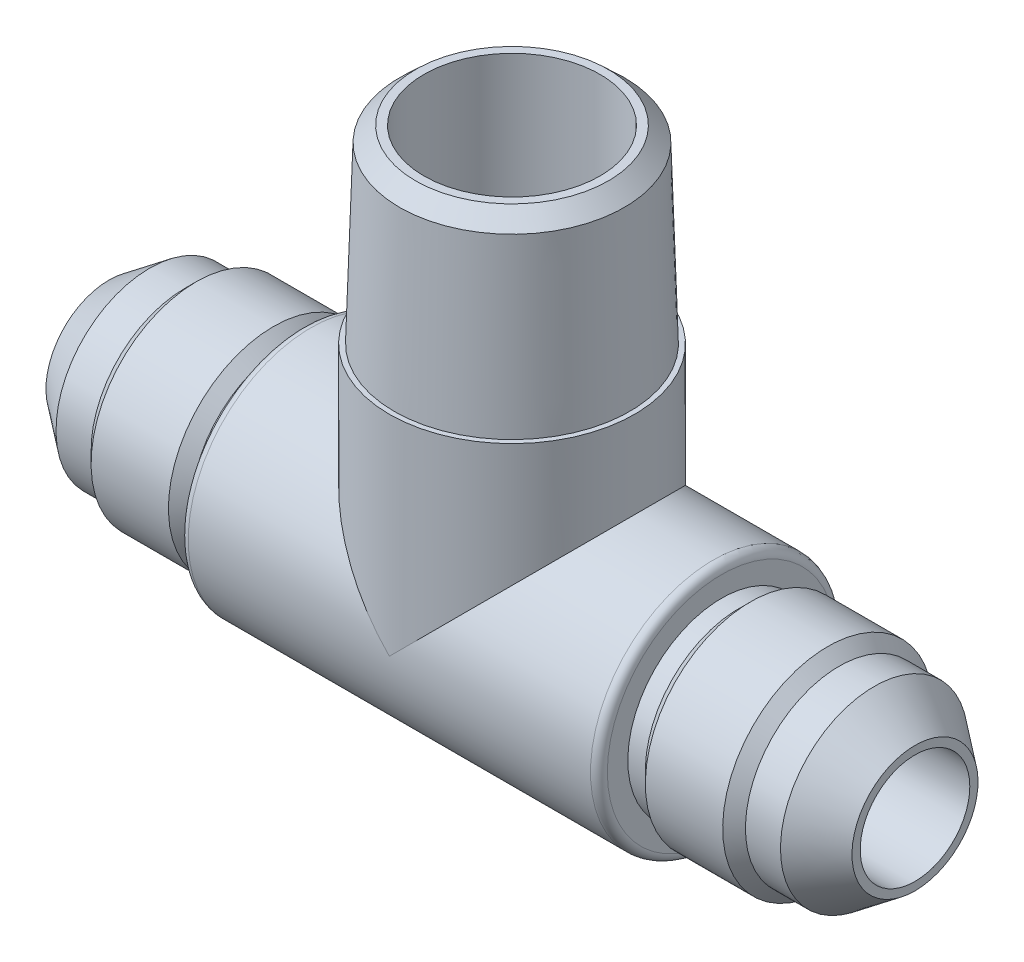
SolidWorks part; units mm, degrees
ref_plane "Front Plane" through (0, 0, 0) normal (0, 0, 1) x (1, 0, 0)
ref_plane "Top Plane" through (0, 0, 0) normal (0, 1, 0) x (1, 0, 0)
ref_plane "Right Plane" through (0, 0, 0) normal (1, 0, 0) x (0, 0, -1)
sketch "Sketch1" plane through (0, 0, 0) normal (0, 0, 1) x (1, 0, 0)
  line L0 (0, 0) -> (-18.9865, 0) construction
  line L1 (0, 0) -> (0, 18.9865) construction
  line L2 (-9.525, 18.9865) -> (9.525, 18.9865) construction
  line L3 (-18.9865, 9.525) -> (-18.9865, -9.525) construction
  line L6 (-36.5125, 9.525) -> (-36.5125, -9.525) construction
  line L8 (-10.668, 36.1163) -> (10.668, 36.1163) construction
  line L9 (0, 0) -> (0, 36.1163) construction
  line L10 (-18.9865, 11.1125) -> (-18.9865, -11.1125) construction
  line L12 (-11.1125, 18.9865) -> (11.1125, 18.9865) construction
  point P15 (0, 22.5603)
  dimension "S" = 17.526
  dimension "Pipe Thread Dia" = 21.336
  dimension "V" = 36.1163
  dimension "TE" = 13.556
  dimension "OA" = 22.225
ref_plane "Plane1" through (-36.5125, 0, 0) normal (1, 0, 0) x (0, 0, -1)
sketch "Sketch2" plane through (-36.5125, 0, 0) normal (1, 0, 0) x (0, 0, -1)
  circle A0 centre (0, 0) radius 9.525
  dimension "Thread OD" = 19.05
extrude "Extrude1" add sketch "Sketch2" along normal up to vertex (17.526 mm away) up to point (-18.9865, 0, 0)
sketch "Sketch3" plane through (-36.5125, 0, 0) normal (-1, 0, 0) x (0, 0, 1)
  circle A0 centre (0, 0) radius 9.525 construction
  circle A1 centre (0, 0) radius 9.525
curve "Helix/Spiral1" pitch 1.5875 height 36.5125 turns 23 parameters "pitch"=1.5875
sketch "Sketch4" plane through (0, 0, 0) normal (0, 0, 1) x (1, 0, 0)
  line L0 (-37.9016, 9.525) -> (-37.3062, 8.4939)
  line L1 (-37.3062, 8.4939) -> (-37.1078, 8.4939)
  line L2 (-37.1078, 8.4939) -> (-36.5125, 9.525)
  line L3 (-37.9016, 9.525) -> (-36.5125, 9.525)
  line L6 (-37.207, 9.525) -> (-37.207, 8.4939) construction
  line L7 (-37.6039, 9.0094) -> (-36.8102, 9.0094) construction
  line L8 (-36.5125, 9.525) -> (-36.5125, -9.525) construction
  dimension "D1" = 0.1984
  dimension "D2" = 0.7937
  dimension "D3" = 60
sweep "Cut-Sweep1" [suppressed] cut profiles "Sketch4" path "Helix/Spiral1"
sketch "Sketch5" plane through (0, 0, 0) normal (0, 0, 1) x (1, 0, 0)
  line L0 (-36.5125, 6.35) -> (-36.5125, -6.35) construction
  line L1 (-32.8189, 8.4939) -> (-29.6439, 8.4939)
  line L2 (-29.6439, 8.4939) -> (-28.6128, 9.525)
  line L3 (-36.5125, 5.7106) -> (-36.5125, -5.7106) construction
  line L4 (-28.6128, 9.525) -> (-36.5125, 9.525)
  line L5 (-37.9016, 9.525) -> (-36.5125, 9.525) construction
  line L6 (-18.9865, 9.525) -> (-18.9865, -9.525) construction
  line L7 (-18.9865, 8.4939) -> (-20.574, 8.4939)
  line L8 (-20.574, 8.4939) -> (-21.6051, 9.525)
  line L9 (-21.6051, 9.525) -> (-18.9865, 9.525)
  line L10 (-18.9865, 8.4939) -> (-18.9865, 9.525)
  line L11 (-27.2626, -9.525) -> (-27.2626, 0) construction
  line L12 (-18.9865, 0) -> (-36.5125, 0) construction
  line L13 (-36.5125, 9.525) -> (-36.5125, -9.525) construction
  line L14 (-36.5125, 5.7106) -> (-32.8189, 8.4939)
  line L15 (-36.5125, 9.525) -> (-36.5125, 5.7106)
  line L16 (0, 0) -> (-18.9865, 0) construction
  point P16 (-27.2626, -9.525)
  dimension "D3" = 45
  dimension "D5" = 45
  dimension "D6" = 1.5875
  dimension "Tube OD" = 12.7
  dimension "D2" = 11.4211
  dimension "D1" = 37
  dimension "D4" = 3.175
  dimension "D7" = 2.3813
revolve "Cut-Revolve1" cut sketch "Sketch5" angle 360 about L0
ref_plane "Plane2" through (-18.9865, 0, 0) normal (1, 0, 0) x (0, 0, -1)
sketch "Sketch15" plane through (-18.9865, 0, 0) normal (1, 0, 0) x (0, 0, -1)
  circle A0 centre (0, 0) radius 11.1125
extrude "Boss-Extrude1" add sketch "Sketch15" along normal up to vertex (18.9865 mm away) up to point (0, 0, 0)
sketch "Sketch16" plane through (0, 0, 0) normal (1, 0, 0) x (0, 0, -1)
  circle A0 centre (0, 0) radius 4.9657
  dimension "Min ID" = 9.9314
extrude "Cut-Extrude1" cut sketch "Sketch16" against normal through all
ref_plane "Plane3" through (0, 18.9865, 0) normal (0, 1, 0) x (-1, 0, 0)
sketch "Sketch20" plane through (0, 18.9865, 0) normal (0, 1, 0) x (-1, 0, 0)
  circle A0 centre (0, 0) radius 11.1125
extrude "Boss-Extrude2" add sketch "Sketch20" against normal up to vertex (18.9865 mm away) separate body up to point (0, 0, 0)
sketch "Sketch22" plane through (0, 18.9865, 0) normal (0, 1, 0) x (-1, 0, 0)
  circle A0 centre (0, 0) radius 10.668
extrude "Boss-Extrude3" add sketch "Sketch22" along normal up to vertex (17.1298 mm away) draft 1.75 separate body up to point (0, 36.1163, 0)
sketch "Sketch23" plane through (0, 36.1163, 0) normal (0, 1, 0) x (1, 0, 0)
  circle A0 centre (0, 0) radius 10.1446 construction
  circle A1 centre (0, 0) radius 10.1446
curve "Helix/Spiral2" parameters "Pitch"=1.8143
chamfer "Chamfer1" distance 1.3607 angle 45 1 edges at (0, 36.1163, 10.1446) first distance on face at (0, 36.1163, 10.1446)
sketch "Sketch25" plane through (0, 18.9865, 0) normal (0, -1, 0) x (1, 0, 0)
  circle A1 centre (0, 0) radius 10.668
  circle A2 centre (0, 0) radius 10.668
  dimension "D1" = 0
sketch "Sketch24" plane through (0, 0, 0) normal (0, 0, 1) x (1, 0, 0)
  line L0 (10.2428, 37.8738) -> (10.2428, 36.0596) construction
  line L1 (10.2428, 36.0596) -> (8.6716, 36.9667) construction
  line L2 (8.6716, 36.9667) -> (10.2428, 37.8738) construction
  line L3 (8.868, 37.0801) -> (8.868, 36.8533)
  line L4 (8.6716, 36.9667) -> (8.868, 36.9667) construction
  line L5 (10.0464, 37.7605) -> (10.0464, 36.173) construction
  line L6 (10.0464, 36.9667) -> (10.2428, 36.9667) construction
  line L7 (10.1446, 36.9667) -> (10.1446, 36.1163) construction
  line L8 (10.1446, 37.8172) -> (10.2428, 36.0596)
  line L9 (10.2428, 36.0596) -> (8.868, 36.8533)
  line L10 (8.868, 37.0801) -> (10.1446, 37.8172)
  dimension "D1" = 1.8143
  dimension "D2" = 0.2268
sweep "Cut-Sweep2" [suppressed] cut profiles "Sketch24" path "Helix/Spiral2"
extrude "Boss-Extrude4" add sketch "Sketch25" against normal up to vertex (17.1298 mm away) draft 15 up to point (10.668, 36.1163, 0)
sketch "Sketch28" plane through (0, 36.1163, 0) normal (0, 1, 0) x (1, 0, 0)
  circle A2 centre (0, 0) radius 7.9784
  circle A3 centre (0, 0) radius 7.9784
  dimension "D1" = 0.762
extrude "Cut-Extrude6" cut sketch "Sketch28" against normal up to vertex (17.1298 mm away) up to point (0, 18.9865, 0)
fillet "Fillet1" radius 0.762 1 edges at (-18.9865, 0, -11.1125)
sketch "Sketch10" plane through (0, 0, 0) normal (1, 0, 0) x (0, 0, -1)
  line L0 (0, 0) -> (-12.651, 0) construction
ref_axis "Axis1" through (0, 0, 12.651) along (0, 0, -1)
pattern_circular "CirPattern1" count 2 over 180 about axis through (0, 0, 12.651) along (0, 0, -1) reverse direction yes of bodies 110 103
combine bodies "Combine2" operation type add bodies to combine 110 122 114 105
sketch "Sketch30" plane through (0, 0, 0) normal (0, 0, 1) x (1, 0, 0)
  line L0 (0, 18.9865) -> (0, 9.4932)
  line L1 (0, 18.9865) -> (-10.922, 18.9865)
  line L2 (0, 0) -> (0, 18.9865) construction
  line L3 (-10.922, 18.9865) -> (0, 9.4932) construction
  line L4 (-5.461, 14.2399) -> (-6.1275, 13.4731) construction
  line L5 (-10.922, 18.9865) -> (-10.922, 18.4785)
  arc A0 (-10.922, 18.4785) -> (0, 9.4932) centre (13.649, 37.215) ccw
  point P2 (0, 9.4932)
  dimension "D1" = 0.254
  dimension "D2" = 1.016
  dimension "D3" = 0.508
revolve "Revolve1" add sketch "Sketch30" angle 360 about L0
sketch "Sketch26" plane through (-36.5125, 0, 0) normal (-1, 0, 0) x (0, 0, 1)
  circle A0 centre (0, 0) radius 4.9657 construction
  circle A1 centre (0, 0) radius 4.9657
extrude "Cut-Extrude4" cut sketch "Sketch26" against normal through all
sketch "Sketch29" plane through (0, 0, 0) normal (0, 1, 0) x (1, 0, 0)
  circle A0 centre (0, 0) radius 4.9657
  dimension "D1" = 9.9314
extrude "Cut-Extrude7" cut sketch "Sketch29" along normal through all
sketch "Sketch12" plane through (0, 0, 0) normal (0, 0, 1) x (1, 0, 0)
  line L0 (0, 0) -> (0, 36.1163) construction
  line L2 (0, 0) -> (-36.5125, 0) construction
  line L3 (7.9784, 36.1163) -> (-7.9784, 36.1163) construction
sketch "Sketch13" plane through (0, 0, 0) normal (1, 0, 0) x (0, 0, -1)
  line L0 (9.525, 18.9865) -> (-9.525, 18.9865)
  line L1 (0, 0) -> (0, 18.9865) construction
  line L3 (9.525, 0) -> (-9.525, 0)
  circle A0 centre (0, 0) radius 4.9657
  circle A1 centre (0, 0) radius 4.9657 construction
  dimension "D1" = 19.05
sketch "Sketch31" plane through (-36.5125, 0, 0) normal (-1, 0, 0) x (0, 0, 1)
  point P0 (0, 0)
sketch "Sketch32" plane through (36.5125, 0, 0) normal (1, 0, 0) x (0, 0, -1)
  point P0 (0, 0)
equation "\"D1@Sketch1\" = \"Thread OD@Sketch2\""
equation "\"D3@Helix/Spiral1\" = \"Q@Sketch1\""
equation "\"D1@Sketch4\" = \"pitch@Helix/Spiral1\"*.125"
equation "\"D2@Sketch4\" = \"pitch@Helix/Spiral1\"*.5"
equation "\"D6@Sketch5\" = \"pitch@Helix/Spiral1\"*1"
equation "\"D4@Sketch5\" = \"pitch@Helix/Spiral1\"*2"
equation "\"D1@Sketch13\" = \"D1@Sketch1\""
equation "\"D7@Sketch5\" = \"pitch@Helix/Spiral1\"*1.5"
equation "\"D2@Sketch5\" = \"Min ID@Sketch16\"*1.15"
equation "\"D1@Sketch24\" = \"Pitch@Helix/Spiral2\""
equation "\"D2@Sketch24\" = \"Pitch@Helix/Spiral2\"/8"
equation "\"D1@Chamfer1\" = \"Pitch@Helix/Spiral2\"*.750"
equation "\"D1@Sketch29\" =  \"Min ID@Sketch16\""
